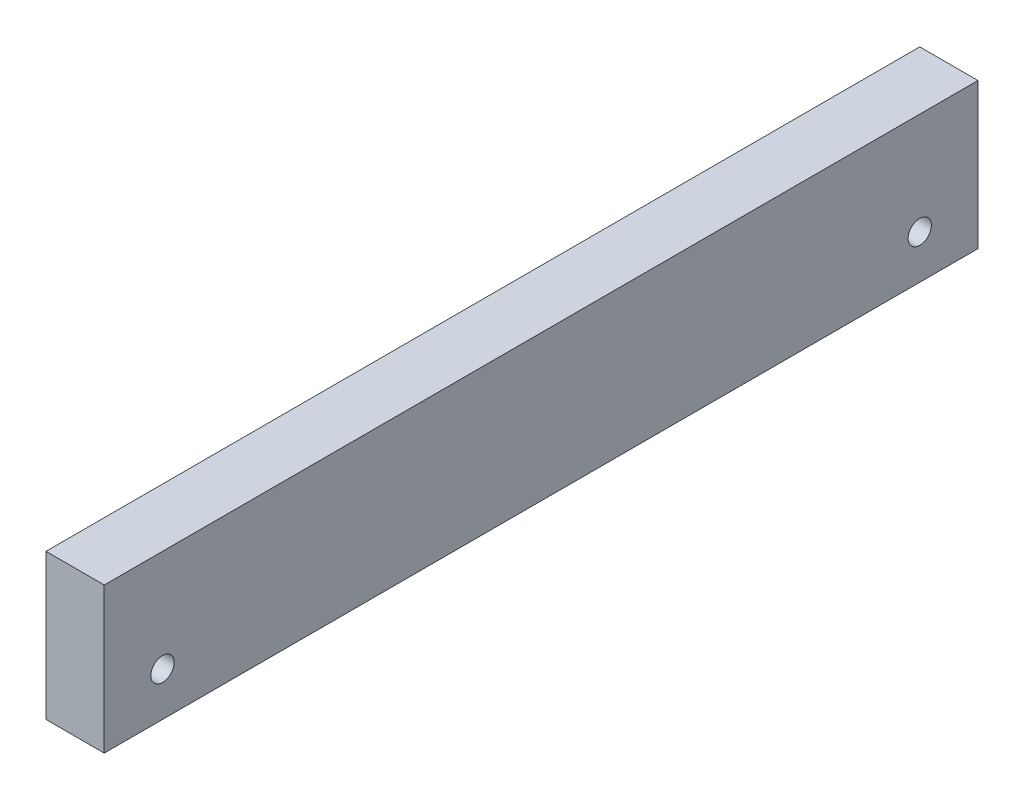
SolidWorks part; units mm, degrees
ref_plane "Front Plane" through (0, 0, 0) normal (0, 0, 1) x (1, 0, 0)
ref_plane "Top Plane" through (0, 0, 0) normal (0, 1, 0) x (1, 0, 0)
ref_plane "Right Plane" through (0, 0, 0) normal (1, 0, 0) x (0, 0, -1)
sketch "Sketch1" plane through (0, 0, 0) normal (0, 0, 1) x (1, 0, 0)
  line L1 (0, 0) -> (20, 0)
  line L2 (0, 0) -> (0, 50)
  line L3 (0, 50) -> (20, 50)
  line L4 (20, 0) -> (20, 50)
  dimension "D1" = 20
  dimension "D2" = 50
extrude "Extrude1" add sketch "Sketch1" along normal blind 300
hole_wizard "Ø8.0 (8) Diameter Hole1" positions "3DSketch1" profile "Sketch2" hole size "Ø8.0" standard "Ansi Metric" end condition through all
sketch3d "3DSketch1"
  line L0 (20, 0, 300) -> (20, 0, 0) construction
  line L1 (20, 0, 0) -> (20, 50, 0) construction
  line L2 (20, 0, 300) -> (20, 50, 300) construction
  point P0 (20, 15, 280)
  point P2 (20, 15, 20)
  dimension "D1" = 15
  dimension "D2" = 15
  dimension "D3" = 20
  dimension "D4" = 20
sketch "Sketch2" plane through (20, 15, 280) normal (0, 1, 0) x (0, 0, -1)
  line L0 (0, 0) -> (0, 20)
  line L1 (0, 20) -> (4, 20)
  line L2 (4, 20) -> (4, 0)
  line L5 (4, 0) -> (0, 0)
  line L11 (0, -6.35) -> (0, 107.95) construction
  dimension "Thru Hole Dia." = 8
  dimension "Thru Hole Depth" = 20
